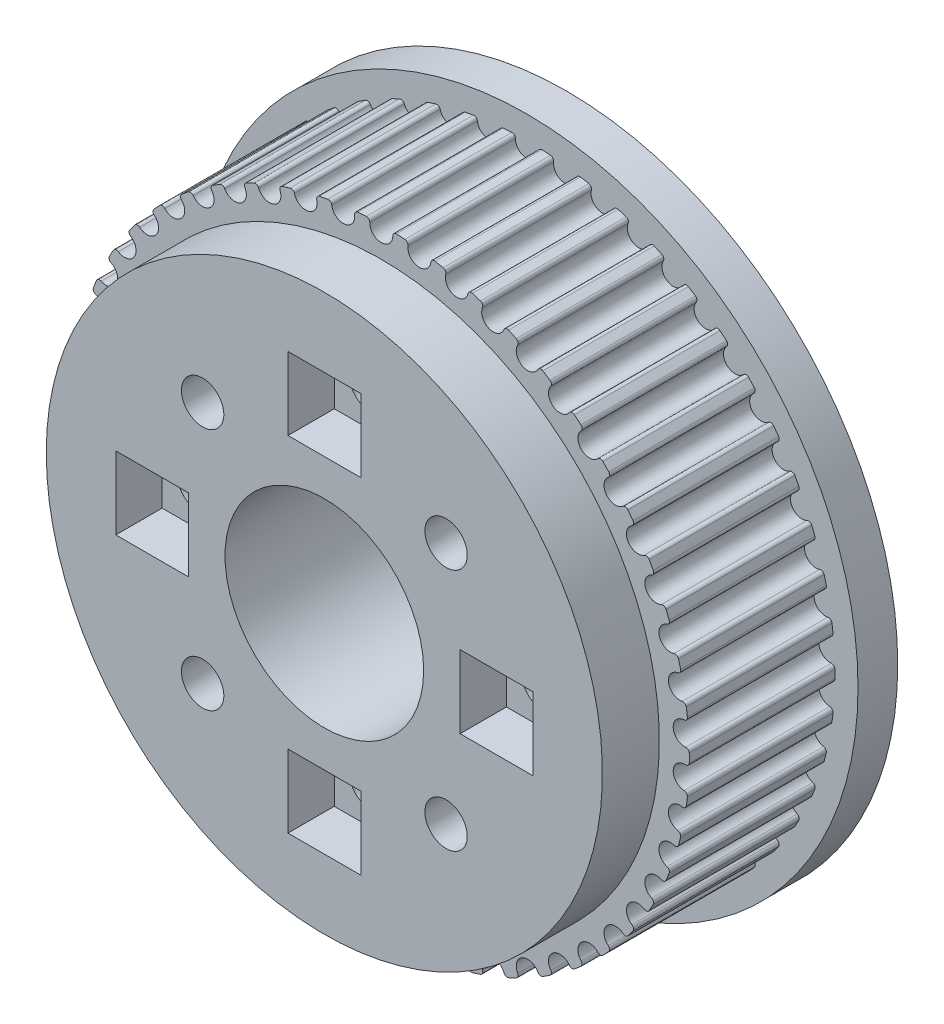
SolidWorks part; units mm, degrees
ref_plane "Front Plane" through (0, 0, 0) normal (1, 0, 0) x (0, 1, 0)
ref_plane "Top Plane" through (0, 0, 0) normal (0, 0, 1) x (0, 1, 0)
ref_plane "Right Plane" through (0, 0, 0) normal (0, 1, 0) x (-1, 0, 0)
sketch "Sketch1" plane through (0, 0, 0) normal (0, 0, 1) x (0, 1, 0)
  line L0 (0, 0) -> (0, 23.2582)
  line L1 (0, 0) -> (1.3869, 22.0447) construction
  line L2 (1.3869, 22.0447) -> (1.4416, 22.9129) construction
  line L3 (2.915, 23.0748) -> (0, 0)
  arc A1 (0.6393, 23.2495) -> (2.2797, 23.1462) centre (1.4416, 22.9129) ccw
  arc A2 (0, 23.2582) -> (0.6393, 23.2495) centre (0, 0) cw
  arc A3 (2.915, 23.0748) -> (2.2797, 23.1462) centre (0, 0) ccw
  dimension "D1" = 3.6
  dimension "D2" = 23.2582
extrude "Boss-Extrude1" add sketch "Sketch1" along normal blind 11 from offset 3
fillet "Fillet1" radius 0.26 2 edges at (-23.2495, 0.6393, 8.5) (-23.1462, 2.2797, 8.5)
pattern_circular "CirPattern1" count 50 over 360 about axis through (0, 0, 14) along (0, 0, -1) of "Fillet1", "Boss-Extrude1"
sketch "Sketch2" plane through (0, 0, 0) normal (0, 0, 1) x (0, 1, 0)
  circle A0 centre (0, 0) radius 25
  circle A1 centre (0, 0) radius 21
  dimension "D1" = 50
  dimension "D2" = 42
extrude "Boss-Extrude2" add sketch "Sketch2" along normal up to surface (3 mm away) contours A1 | A0 A1 region at (0, -24.2929, 0) region at (0, 0, 0) up to face at (0, 0, 3)
extrude "Boss-Extrude3" add sketch "Sketch2<3>" along normal blind 4.3 from surface contours A1 region at (0, 0, 0) starting at face at (0, 0, 14)
sketch "Sketch2<3>" plane through (0, 0, 0) normal (0, 0, 1) x (0, 1, 0) same geometry as "Sketch2"
sketch "Sketch3" plane through (0, 0, 18.3) normal (0, 0, 1) x (1, 0, 0)
  line L0 (15.75, 2.75) -> (15.75, -2.75)
  line L1 (-2.75, 15.75) -> (2.75, 15.75)
  line L2 (-2.75, 15.75) -> (-2.75, 10.25)
  line L3 (-2.75, 10.25) -> (2.75, 10.25)
  line L4 (2.75, 15.75) -> (2.75, 10.25)
  line L5 (-2.75, 15.75) -> (2.75, 10.25) construction
  line L6 (-2.75, 10.25) -> (2.75, 15.75) construction
  line L7 (15.75, 2.75) -> (10.25, 2.75)
  line L8 (10.25, 2.75) -> (10.25, -2.75)
  line L9 (15.75, -2.75) -> (10.25, -2.75)
  line L10 (15.75, 2.75) -> (10.25, -2.75) construction
  line L11 (10.25, 2.75) -> (15.75, -2.75) construction
  line L12 (2.75, -15.75) -> (-2.75, -15.75)
  line L13 (2.75, -15.75) -> (2.75, -10.25)
  line L14 (2.75, -10.25) -> (-2.75, -10.25)
  line L15 (-2.75, -15.75) -> (-2.75, -10.25)
  line L16 (2.75, -15.75) -> (-2.75, -10.25) construction
  line L17 (2.75, -10.25) -> (-2.75, -15.75) construction
  line L18 (-15.75, -2.75) -> (-15.75, 2.75)
  line L19 (-15.75, -2.75) -> (-10.25, -2.75)
  line L20 (-10.25, -2.75) -> (-10.25, 2.75)
  line L21 (-15.75, 2.75) -> (-10.25, 2.75)
  line L22 (-15.75, -2.75) -> (-10.25, 2.75) construction
  line L23 (-10.25, -2.75) -> (-15.75, 2.75) construction
  circle A0 centre (0, 0) radius 13 construction
  circle A1 centre (0, 13) radius 1.6
  circle A10 centre (13, 0) radius 1.6
  circle A11 centre (0, -13) radius 1.6
  circle A12 centre (-13, 0) radius 1.6
  point P18 (0, 0)
  point P33 (0, 0)
  dimension "D1" = 26
  dimension "D2" = 3.2
  dimension "D3" = 5.5
  dimension "D4" = 4
extrude "Cut-Extrude1" cut sketch "Sketch3" against normal through all both and the other way through all contours A1 | A10 | A12 | A11 region at (0, 13, 18.3) region at (13, 0, 18.3) region at (0, -13, 18.3) region at (-13, 0, 18.3)
extrude "Cut-Extrude2" cut sketch "Sketch3<3>" against normal blind 3.5 and the other way through all contours A12 | A1 | L21 L18 L19 L20 A12 | L4 L1 L2 L3 A1 | L9 L0 L7 L8 A10 | L15 L12 L13 L14 A11 | A11 | A10 region at (15.6722, 0, 18.3) region at (0, 15.6722, 18.3) region at (0, -15.6722, 18.3) region at (-15.6722, 0, 18.3) region at (0, 13, 18.3) region at (13, 0, 18.3) region at (0, -13, 18.3) region at (-13, 0, 18.3)
sketch "Sketch3<3>" plane through (0, 0, 18.3) normal (0, 0, 1) x (1, 0, 0) same geometry as "Sketch3"
sketch "Sketch4" plane through (0, 0, 0) normal (0, 0, -1) x (1, 0, 0)
  line L0 (0, 0) -> (9.1924, 9.1924) construction
  line L1 (11.9424, -11.9424) -> (6.4424, -11.9424)
  line L2 (6.4424, 11.9424) -> (11.9424, 11.9424)
  line L3 (6.4424, 11.9424) -> (6.4424, 6.4424)
  line L4 (6.4424, 6.4424) -> (11.9424, 6.4424)
  line L5 (11.9424, 11.9424) -> (11.9424, 6.4424)
  line L6 (6.4424, 11.9424) -> (11.9424, 6.4424) construction
  line L7 (6.4424, 6.4424) -> (11.9424, 11.9424) construction
  line L8 (6.4424, -6.4424) -> (6.4424, -11.9424)
  line L9 (11.9424, -6.4424) -> (6.4424, -6.4424)
  line L10 (11.9424, -6.4424) -> (11.9424, -11.9424)
  line L11 (-11.9424, -11.9424) -> (-11.9424, -6.4424)
  line L12 (-6.4424, -6.4424) -> (-11.9424, -6.4424)
  line L13 (-6.4424, -11.9424) -> (-6.4424, -6.4424)
  line L14 (-6.4424, -11.9424) -> (-11.9424, -11.9424)
  line L15 (-11.9424, 11.9424) -> (-6.4424, 11.9424)
  line L16 (-6.4424, 6.4424) -> (-6.4424, 11.9424)
  line L17 (-11.9424, 6.4424) -> (-6.4424, 6.4424)
  line L18 (-11.9424, 6.4424) -> (-11.9424, 11.9424)
  circle A0 centre (0, 0) radius 13 construction
  circle A1 centre (9.1924, 9.1924) radius 1.6
  circle A2 centre (9.1924, -9.1924) radius 1.6
  circle A3 centre (-9.1924, -9.1924) radius 1.6
  circle A4 centre (-9.1924, 9.1924) radius 1.6
  point P31 (0, 0)
  dimension "D2" = 3.2
  dimension "D1" = 5.5
  dimension "D3" = 4
extrude "Cut-Extrude3" cut sketch "Sketch4" against normal through all contours A4 | A1 | A2 | A3 region at (9.1924, -9.1924, 0) region at (9.1924, 9.1924, 0) region at (-9.1924, 9.1924, 0) region at (-9.1924, -9.1924, 0)
extrude "Cut-Extrude4" cut sketch "Sketch4<3>" against normal blind 3
sketch "Sketch4<3>" plane through (0, 0, 0) normal (0, 0, -1) x (1, 0, 0) same geometry as "Sketch4"
sketch "Sketch5" plane through (0, 0, 18.3) normal (0, 0, 1) x (1, 0, 0)
  circle A0 centre (0, 0) radius 7.5
  dimension "D1" = 15
extrude "Cut-Extrude5" cut sketch "Sketch5" against normal through all contours A0
equation "\"D2@Sketch1\"=(50*3) / (PI * 2) - 0.615"
